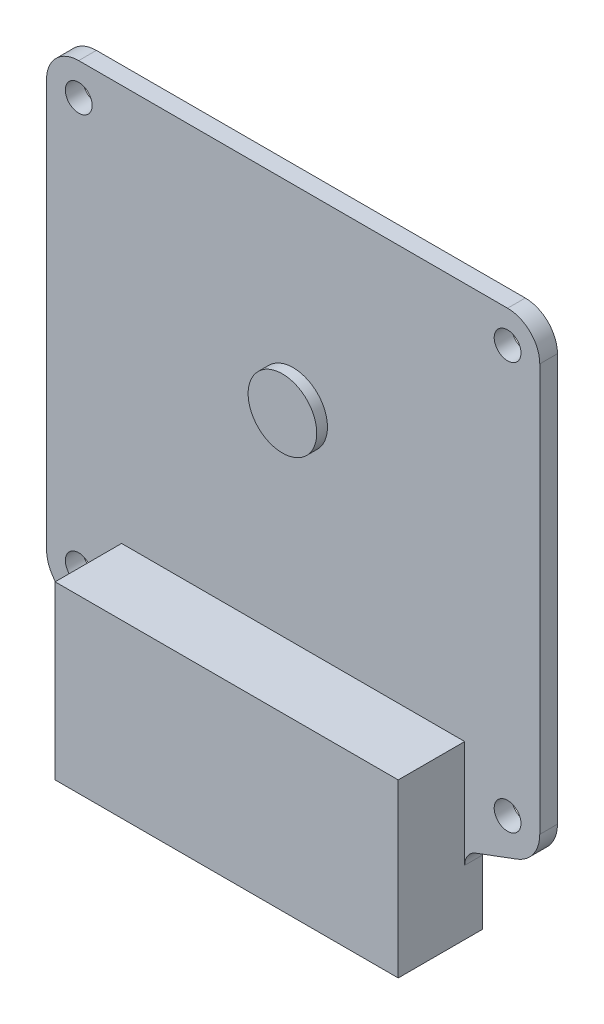
SolidWorks part; units mm, degrees
ref_plane "Front Plane" through (0, 0, 0) normal (0, 0, 1) x (1, 0, 0)
ref_plane "Top Plane" through (0, 0, 0) normal (0, 1, 0) x (1, 0, 0)
ref_plane "Right Plane" through (0, 0, 0) normal (1, 0, 0) x (0, 0, -1)
sketch "Sketch1" plane through (0, 0, 0) normal (0, 0, 1) x (1, 0, 0)
  line L0 (-20, 15) -> (20, 15) construction
  line L1 (-20, -23) -> (20, -23) construction
  line L2 (-20, 18) -> (20, 18)
  line L3 (-16, -35) -> (16, -35)
  line L4 (-23, 15) -> (-23, -23)
  line L5 (23, 15) -> (23, -23)
  line L6 (-27.3518, -23) -> (-27.3518, -29) construction
  line L7 (-27.3518, -29) -> (-27.3518, -35) construction
  line L8 (-27.3518, -29) -> (32.2638, -29) construction
  line L9 (-27.3518, -35) -> (32.2638, -35) construction
  line L10 (-16, -35) -> (-16, -29)
  line L11 (16, -35) -> (16, -29)
  line L12 (-20.8734, -26.0636) -> (-17.0471, -27.4916)
  line L13 (0, 21.7483) -> (0, -55.2269) construction
  line L15 (20.8734, -26.0636) -> (17.0471, -27.4916)
  circle A0 centre (0, 0) radius 3.2
  circle A1 centre (20, 15) radius 1.25
  circle A2 centre (-20, 15) radius 1.25
  circle A3 centre (-20, -23) radius 1.25
  circle A4 centre (20, -23) radius 1.25
  arc A5 (-20, 18) -> (-23, 15) centre (-20, 15) ccw
  arc A6 (23, 15) -> (20, 18) centre (20, 15) ccw
  arc A8 (-16, -29) -> (-17.0471, -27.4916) centre (-17.61, -29) ccw
  arc A9 (16, -29) -> (17.0471, -27.4916) centre (17.61, -29) cw
  arc A11 (-23, -23) -> (-20.8734, -26.0636) centre (-19.73, -23) ccw
  arc A12 (23, -23) -> (20.8734, -26.0636) centre (19.73, -23) cw
  point P5 (0, 15)
  point P10 (0, -23)
  point P18 (0, -35)
  dimension "D1" = 15
  dimension "D3" = 2.5
  dimension "D4" = 2.5
  dimension "D7" = 2.5
  dimension "D8" = 2.5
  dimension "D11" = 6
  dimension "D9" = 6
  dimension "D12" = 6.4
  dimension "D15" = 3.27
  dimension "D16" = 1.61
  dimension "D2" = 40
  dimension "D5" = 40
  dimension "D6" = 23
  dimension "D10" = 32
  dimension "D13" = 6
  dimension "D14" = 6
  dimension "D17" = 7.3518
extrude "Boss-Extrude1" add sketch "Sketch1" along normal blind 1.65
sketch "Sketch2" plane through (0, 0, 1.65) normal (0, 0, 1) x (1, 0, 0)
  line L0 (-16, -35) -> (16, -35) construction
  line L1 (-16, -19) -> (16, -19)
  line L2 (-16, -19) -> (-16, -35)
  line L3 (-16, -35) -> (16, -35)
  line L4 (16, -19) -> (16, -35)
  line L5 (-16, -19) -> (16, -35) construction
  line L6 (-16, -35) -> (16, -19) construction
  point P0 (0, -27)
  dimension "D1" = 16
  dimension "D2" = 32
extrude "Boss-Extrude2" add sketch "Sketch2" along normal blind 6.2
extrude "Boss-Extrude3" add sketch "Sketch1<2>" along normal offset from surface (2.65 mm away) 1 contours A0 region at (0, 0, 0) up to face at (0, -13.0147, 1.65) offset beyond the face yes
sketch "Sketch1<2>" plane through (0, 0, 0) normal (0, 0, 1) x (1, 0, 0) same geometry as "Sketch1"
